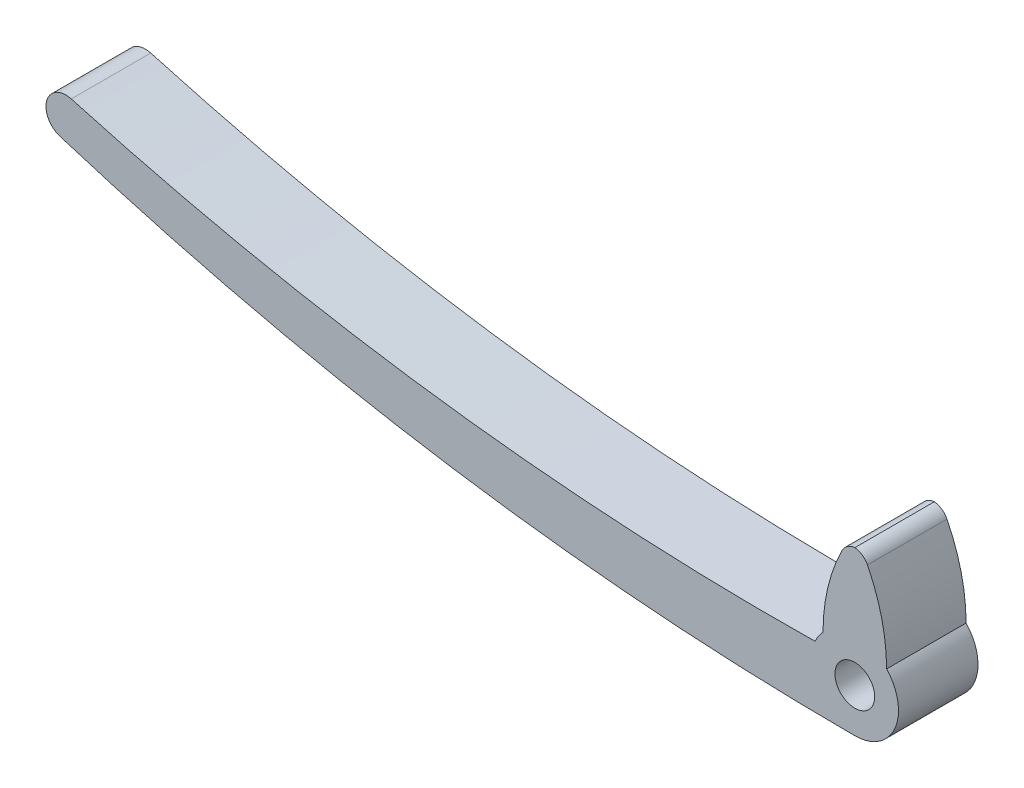
SolidWorks part; units mm, degrees
ref_plane "Front Plane" through (0, 0, 0) normal (0, 0, 1) x (1, 0, 0)
ref_plane "Top Plane" through (0, 0, 0) normal (0, 1, 0) x (1, 0, 0)
ref_plane "Right Plane" through (0, 0, 0) normal (1, 0, 0) x (0, 0, -1)
sketch "Sketch1" plane through (0, 0, 0) normal (0, 0, 1) x (1, 0, 0)
  line L0 (0, 15) -> (0, 0) construction
  line L1 (-1, 15) -> (1, 15)
  line L2 (-4, 3.7749) -> (-4, 14.0896) construction
  line L3 (0, 0) -> (-66.7842, 0) construction
  line L4 (0, 0) -> (-99.2546, 12.1869) construction
  circle A0 centre (0, 0) radius 2.5
  circle A1 centre (0, 0) radius 5.5
  arc A2 (-1, 15) -> (-4, 3.7749) centre (18.5004, 3.7749) ccw
  arc A3 (1, 15) -> (4, 3.7749) centre (-18.5004, 3.7749) cw
  arc A4 (0, -5.5) -> (-100.0022, 9.8011) centre (0, 328.9391) cw
  arc A6 (-98.5723, 14.5923) -> (-100.0022, 9.8011) centre (-99.2546, 12.1869) ccw
  arc A7 (-98.5723, 14.5923) -> (-5, 2.2913) centre (-9.8751, 327.2547) ccw
  dimension "D1" = 5
  dimension "D4" = 8
  dimension "D7" = 5
  dimension "D8" = 5
  dimension "D10" = 325
  dimension "D2" = 3
  dimension "D3" = 2
  dimension "D5" = 15
  dimension "D6" = 100
  dimension "D9" = 83
sketch "Sketch2" plane through (0, 0, 0) normal (0, 0, 1) x (1, 0, 0)
  line L0 (-1, 15) -> (1, 15) construction
  line L1 (-1, 15) -> (1, 15)
  line L2 (0, 28.604) -> (0, -22.6297) construction
  arc A0 (-100.0022, 9.8011) -> (0, -5.5) centre (0, 328.9391) ccw construction
  circle A1 centre (0, 0) radius 5.5
  arc A2 (0, -5.5) -> (4, 3.7749) centre (0, 0) ccw
  circle A3 centre (0, 0) radius 2.5
  circle A4 centre (0, 0) radius 2.5
  arc A5 (-98.5723, 14.5923) -> (-100.0022, 9.8011) centre (-99.2546, 12.1869) ccw construction
  arc A6 (-98.5723, 14.5923) -> (-5, 2.2913) centre (-9.8751, 327.2547) ccw construction
  arc A7 (4, 3.7749) -> (1, 15) centre (-18.5004, 3.7749) ccw construction
  arc A8 (-1, 15) -> (-4, 3.7749) centre (18.5004, 3.7749) ccw construction
  arc A9 (-100.0022, 9.8011) -> (0, -5.5) centre (0, 328.9391) ccw
  arc A10 (-98.5723, 14.5923) -> (-100.0022, 9.8011) centre (-99.2546, 12.1869) ccw
  arc A11 (-98.5723, 14.5923) -> (-5, 2.2913) centre (-9.8751, 327.2547) ccw
  arc A12 (4, 3.7749) -> (1, 15) centre (-18.5004, 3.7749) ccw
  arc A13 (-1, 15) -> (-4, 3.7749) centre (18.5004, 3.7749) ccw
  arc A14 (-4, 3.7749) -> (-5, 2.2913) centre (0, 0) ccw
  dimension "D1" = 0
  dimension "D2" = 0
extrude "Boss-Extrude1" add sketch "Sketch2" along normal mid plane 10
fillet "Fillet1" radius 2 2 edges at (1, 15, 0) (-1, 15, 0)
